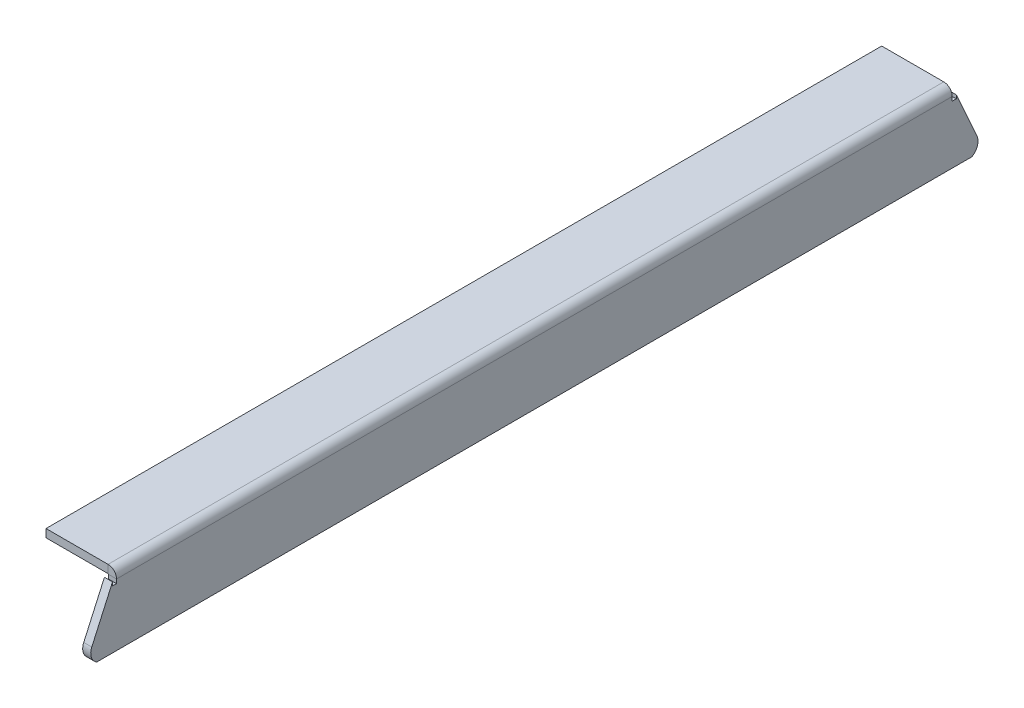
SolidWorks part; units mm, degrees
note: The reader was unsure of these and kept them because the rebuilt part matched: flange length of "Edge-Flange1".
material "ASTM A36 Steel"
ref_plane "Front Plane" through (0, 0, 0) normal (0, 0, 1) x (1, 0, 0)
ref_plane "Top Plane" through (0, 0, 0) normal (0, 1, 0) x (1, 0, 0)
ref_plane "Right Plane" through (0, 0, 0) normal (1, 0, 0) x (0, 0, -1)
sketch "Sketch1" plane through (0, 0, 0) normal (1, 0, 0) x (0, 0, -1)
  line L0 (175.1945, 25.0107) -> (-239.5718, 25.0107)
  line L1 (184.9416, -9.9893) -> (-249.3189, -9.9893)
  line L2 (187.4672, -2.3041) -> (175.1945, 25.0107)
  line L3 (-251.8444, -2.3041) -> (-239.5718, 25.0107)
  arc A0 (184.9416, -9.9893) -> (187.4672, -2.3041) centre (181.9942, -4.7632) ccw
  arc A1 (-251.8444, -2.3041) -> (-249.3189, -9.9893) centre (-246.3715, -4.7632) ccw
base flange "Base-Flange1" sketch "Sketch1" thickness 4 reverse thickness direction no parameters "D1"=0.2
edge flange "Edge-Flange1" sketch "Sketch8" flange angle 90 flange length 35 flange position material inside bend radius 0.2 thickness 4 relief rectangular parameters "D6"=10
sketch "Sketch8" plane through (-4, 25.0107, 0) normal (0, -1, 0) x (0, 0, 1)
  line L2 (-175.1945, 0) -> (-175.1945, 31)
  line L3 (-175.1945, 31) -> (239.5718, 31)
  line L4 (239.5718, 31) -> (239.5718, 0)
  line L5 (239.5718, 0) -> (-175.1945, 0) construction
  line L6 (239.5718, 0) -> (-175.1945, 0)
bend "EdgeBend1" bend radius 0.2 bend angle 90 parameters "D5"=1
sketch "Bend-Lines1" [suppressed] plane through (0, 0, 0) normal (0, 1, 0) x (1, 0, 0)
sketch "Bounding-Box1" [suppressed] plane through (0, 0, 0) normal (0, 1, 0) x (1, 0, 0)
sheet metal parameters "Sheet-Metal1" thickness 4 parameters "D1"=0.2
flat pattern "Flat-Pattern1" [suppressed]
sketch "Bend-Lines2" plane through (0, 0, 0) normal (0, 1, 0) x (1, 0, 0)
sketch3d "Bounding-Box2" [suppressed]
  line L0 (5.9999, 29.7744, 0) -> (-434.3656, 29.7738, 0) construction
  line L1 (5.9999, -5.2256, 0) -> (-434.3655, -5.2262, 0) construction
  line L2 (5.9999, 29.7744, 0) -> (5.9999, -5.2256, 0) construction
  line L3 (-434.3656, 29.7738, 0) -> (-434.3655, -5.2262, 0) construction
sheet metal parameters "Sheet-Metal2" thickness 4 parameters "D1"=0.2
flat pattern "Flat-Pattern1"
sketch "Bend-Lines2" plane through (0, 0, 0) normal (1, 0, 0) x (0, 0, -1)
  line L0 (175.1945, 22.5386) -> (-239.5718, 22.5386) construction
  line L1 (175.1945, 22.5386) -> (-239.5718, 22.5386) construction
sketch3d "Bounding-Box2" [suppressed]
  line L0 (-5.9998, 59.8302, 0) -> (434.3656, 59.8296, 0) construction
  line L1 (-5.9999, -5.2256, 0) -> (434.3655, -5.2262, 0) construction
  line L2 (-5.9998, 59.8302, 0) -> (-5.9999, -5.2256, 0) construction
  line L3 (434.3656, 59.8296, 0) -> (434.3655, -5.2262, 0) construction
bend of the flat pattern "Flatten-<EdgeBend1>1"
